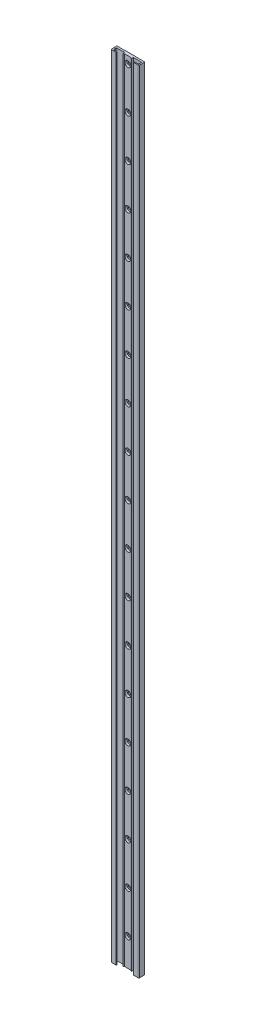
SolidWorks part; units mm, degrees
ref_plane "Front Plane" through (0, 0, 0) normal (0, 0, 1) x (1, 0, 0)
ref_plane "Top Plane" through (0, 0, 0) normal (0, 1, 0) x (1, 0, 0)
ref_plane "Right Plane" through (0, 0, 0) normal (1, 0, 0) x (0, 0, -1)
ref_plane "Plane4" through (0, 0, 8.7) normal (0, 0, 1) x (1, 0, 0)
sketch "Sketch1" plane through (0, 0, 8.7) normal (0, 0, 1) x (1, 0, 0)
  line L0 (-20, 0) -> (20, 0)
  line L1 (20, 0) -> (20, 1130.3)
  line L2 (20, 1130.3) -> (-20, 1130.3)
  line L3 (-20, 1130.3) -> (-20, 0)
  dimension "D1" = 1130.3
extrude "Boss-Extrude1" add sketch "Sketch1" against normal blind 8.7
sketch "Sketch2" plane through (0, 0, 0) normal (0, -1, 0) x (1, 0, 0)
  line L0 (12.5, 8.7) -> (-12.5, 8.7)
  line L1 (-12.5, 8.7) -> (-12.5, 7.2)
  line L2 (-12.5, 7.2) -> (-18, 7.2)
  line L3 (-18, 7.2) -> (-18, 2.8)
  line L4 (-18, 2.8) -> (-6.3, 2.8)
  line L5 (-6.3, 2.8) -> (-6.3, 5.5)
  line L6 (-6.3, 5.5) -> (-4.75, 5.5)
  line L7 (-4.75, 5.5) -> (-4.75, 4.5)
  line L8 (-4.75, 4.5) -> (4.75, 4.5)
  line L9 (4.75, 4.5) -> (4.75, 5.5)
  line L10 (4.75, 5.5) -> (6.3, 5.5)
  line L11 (6.3, 5.5) -> (6.3, 2.8)
  line L12 (6.3, 2.8) -> (18, 2.8)
  line L13 (18, 2.8) -> (18, 7.2)
  line L14 (18, 7.2) -> (12.5, 7.2)
  line L15 (12.5, 7.2) -> (12.5, 8.7)
extrude "Cut-Extrude1" cut sketch "Sketch2" against normal through all
sketch "Sketch3" plane through (0, 0, 0) normal (0, -1, 0) x (1, 0, 0)
  line L0 (8, 0.2) -> (8, 0)
  line L1 (8, 0) -> (20, 0)
  line L2 (20, 0) -> (20, 0.2)
  line L3 (20, 0.2) -> (8, 0.2)
extrude "Cut-Extrude2" cut sketch "Sketch3" against normal through all
sketch "Sketch4" plane through (0, 0, 0) normal (0, -1, 0) x (1, 0, 0)
  line L0 (-8, 0) -> (-8, 0.2)
  line L1 (-8, 0.2) -> (-20, 0.2)
  line L2 (-20, 0.2) -> (-20, 0)
  line L3 (-20, 0) -> (-8, 0)
extrude "Cut-Extrude3" cut sketch "Sketch4" against normal through all
draft "Draft1" type of draft neutral plane draft angle 45 faces to draft 2 face at (4.75, 565.15, 5) face at (-4.75, 565.15, 5) neutral plane through (-4.75, 1130.3, 4.5) neutral plane normal (0, 0, 1) parameters "D1"=45
hole_wizard "CBORE for M4 Hex Head Machine Screw1" positions "Sketch6" profile "Sketch5" counterbore size "M4" standard "ANSI Metric"
sketch "Sketch6" plane through (0, 0, 4.5) normal (0, 0, 1) x (1, 0, 0)
  point P0 (0, 160)
  point P1 (0, 100)
  point P2 (0, 40)
  point P12 (0, 220)
  point P13 (0, 280)
  point P14 (0, 340)
  point P15 (0, 400)
  point P16 (0, 460)
  point P17 (0, 520)
  point P18 (0, 580)
  point P19 (0, 640)
  point P20 (0, 700)
  point P21 (0, 760)
  point P22 (0, 820)
  point P23 (0, 880)
  point P24 (0, 940)
  point P25 (0, 1000)
  point P26 (0, 1060)
  point P27 (0, 1120)
  point P28 (0, 1180)
  dimension "D1" = 18
sketch "Sketch5" plane through (0, 160, 4.5) normal (1, 0, 0) x (0, -1, 0)
  line L0 (0, 0) -> (0, 4.5)
  line L1 (0, 4.5) -> (2.25, 4.5)
  line L3 (2.25, 4.5) -> (2.25, 3.1)
  line L4 (2.25, 3.1) -> (4.25, 3.1)
  line L5 (4.25, 3.1) -> (4.25, 0)
  line L7 (4.25, 0) -> (0, 0)
  line L11 (0, -6.35) -> (0, 107.95) construction
  dimension "Thru Hole Dia." = 4.5
  dimension "Thru Hole Depth" = 4.5
  dimension "C'Bore Dia." = 8.5
  dimension "C'Bore Depth" = 3.1
fillet "Fillet1" radius 0.5 6 edges at (-18, 565.15, 7.2) (-18, 565.15, 2.8) (-20, 565.15, 0.2) (18, 565.15, 7.2) (20, 565.15, 0.2) (18, 565.15, 2.8) tangent propagation no
fillet "Fillet2" radius 1 2 edges at (20, 565.15, 8.7) (-20, 565.15, 8.7) tangent propagation no
ref_plane "Mid_Plane" through (0, 0, 0) normal (1, 0, 0) x (0, 0, -1)
